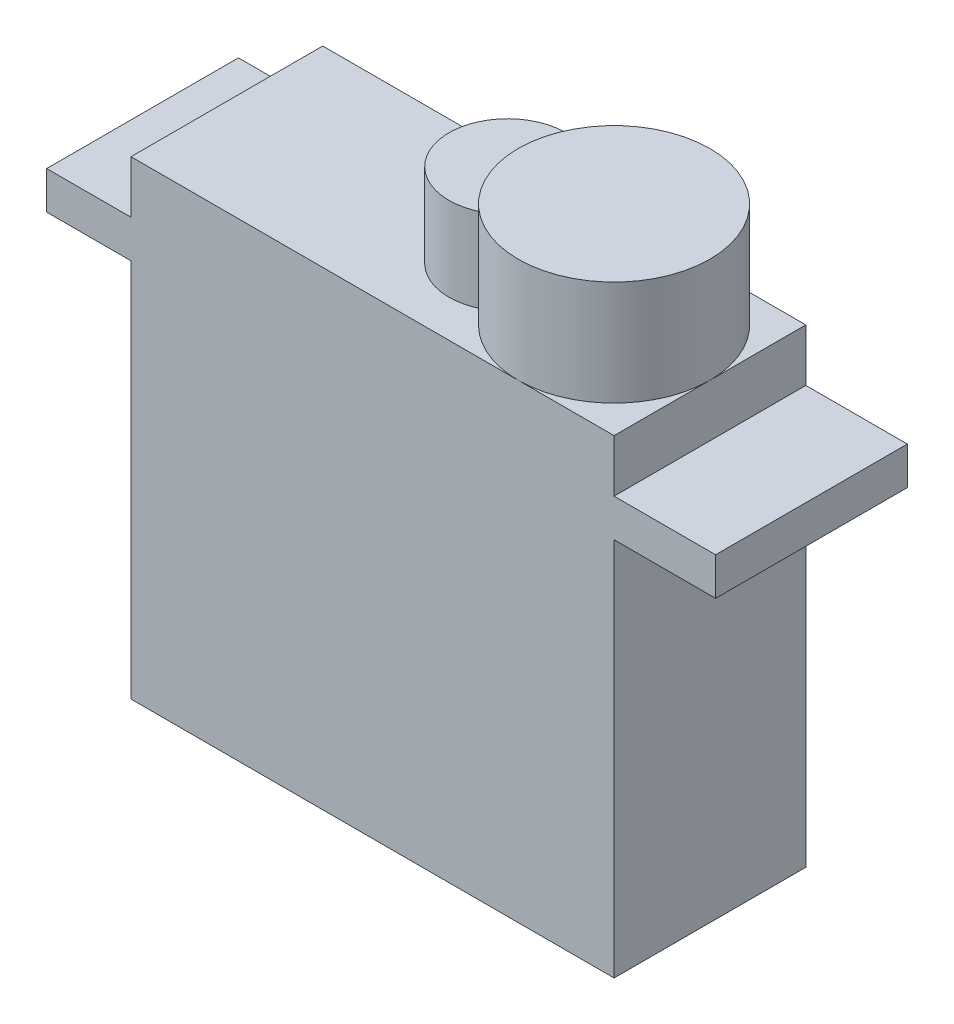
SolidWorks part; units mm, degrees
ref_plane "Front Plane" through (0, 0, 0) normal (0, 0, 1) x (1, 0, 0)
ref_plane "Top Plane" through (0, 0, 0) normal (0, 1, 0) x (1, 0, 0)
ref_plane "Right Plane" through (0, 0, 0) normal (1, 0, 0) x (0, 0, -1)
sketch "Sketch1" plane through (0, 0, 0) normal (0, 1, 0) x (1, 0, 0)
  line L1 (0, 0) -> (23.0378, 0)
  line L2 (0, 0) -> (0, 9.144)
  line L3 (0, 9.144) -> (23.0378, 9.144)
  line L4 (23.0378, 0) -> (23.0378, 9.144)
  dimension "D1" = 23.0378
  dimension "D2" = 9.144
extrude "Boss-Extrude1" add sketch "Sketch1" against normal blind 18.1
sketch "Sketch2" plane through (0, 0, 0) normal (0, 1, 0) x (1, 0, 0)
  line L0 (23.0378, 9.144) -> (0, 9.144) construction
  line L1 (-4.021, 9.144) -> (27.879, 9.144)
  line L2 (-4.021, 9.144) -> (-4.021, 0)
  line L3 (-4.021, 0) -> (27.879, 0)
  line L4 (27.879, 9.144) -> (27.879, 0)
  dimension "D1" = 9.144
  dimension "D2" = 31.9
extrude "Boss-Extrude2" add sketch "Sketch2" along normal blind 1.8
sketch "Sketch3" plane through (0, 1.8, 0) normal (0, 1, 0) x (1, 0, 0)
  line L0 (27.879, 9.144) -> (-4.021, 9.144) construction
  line L1 (0, 0) -> (23.0378, 0)
  line L2 (0, 0) -> (0, 9.144)
  line L3 (0, 9.144) -> (23.0378, 9.144)
  line L4 (23.0378, 0) -> (23.0378, 9.144)
  line L5 (-4.021, 0) -> (27.879, 0) construction
  dimension "D1" = 23.0378
extrude "Boss-Extrude3" add sketch "Sketch3" along normal blind 2.5
sketch "Sketch4" plane through (0, 4.3, 0) normal (0, 1, 0) x (1, 0, 0)
  circle A0 centre (18.4658, 4.572) radius 4.572
  dimension "D1" = 9.144
extrude "Boss-Extrude4" add sketch "Sketch4" along normal blind 5
sketch "Sketch5" plane through (0, 4.3, 0) normal (0, 1, 0) x (1, 0, 0)
  circle A0 centre (13.3858, 4.572) radius 2.794
  circle A1 centre (18.4658, 4.572) radius 4.572 construction
  circle A2 centre (18.4658, 4.572) radius 4.572 construction
  dimension "D2" = 5.588
  dimension "D1" = 5.08
extrude "Boss-Extrude5" add sketch "Sketch5" along normal blind 4
ref_axis "Axis1" through (18.4658, 9.3, -4.572) along (0, -1, 0)
